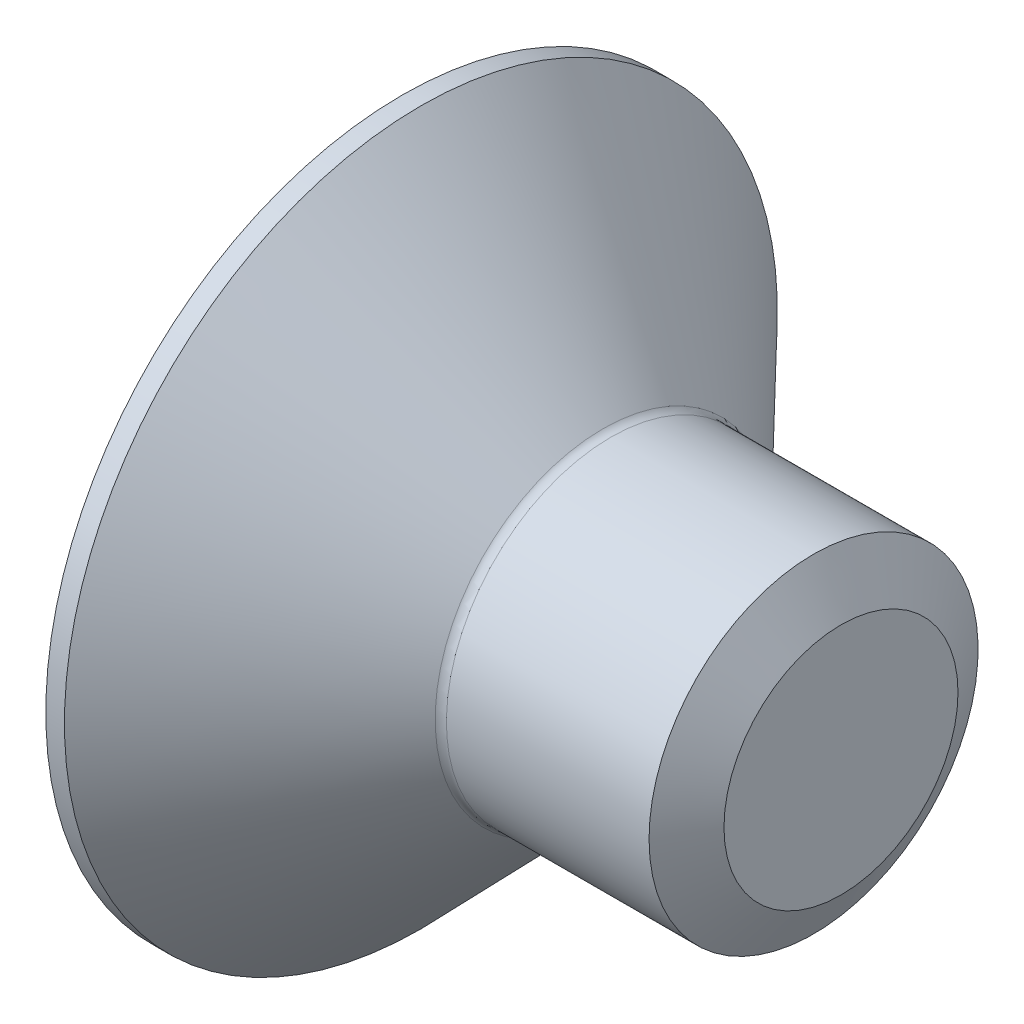
SolidWorks part; units mm, degrees
material "8.8级"
ref_plane "前视基准面" through (0, 0, 0) normal (0, 0, 1) x (1, 0, 0)
ref_plane "上视基准面" through (0, 0, 0) normal (0, 1, 0) x (1, 0, 0)
ref_plane "右视基准面" through (0, 0, 0) normal (1, 0, 0) x (0, 0, -1)
sketch "草图1" plane through (0, 0, 0) normal (0, 0, 1) x (1, 0, 0)
  line L0 (0, 1.5) -> (-2.0976, 1.5)
  line L1 (-2.1695, 1.5305) -> (-3.83, 3.25)
  line L2 (-3.83, 3.25) -> (-4, 3.25)
  line L3 (-4, 3.25) -> (-4, 0)
  line L4 (-4, 0) -> (0, 0)
  line L5 (0, 0) -> (0, 1.5)
  line L6 (0, 0) -> (-4, 0) construction
  arc A0 (-2.0976, 1.5) -> (-2.1695, 1.5305) centre (-2.0976, 1.6) cw
  point P9 (-2.14, 1.5)
  dimension "r" = 0.1
  dimension "k" = 1.86
  dimension "dk" = 6.5
  dimension "l" = 4
  dimension "d" = 3
  dimension "D5" = 46
revolve "旋转1" add sketch "草图1" angle 360 about L6
cosmetic thread "装饰螺纹线1" parameters "b"=6, "D2"=2.58
sketch "草图2" plane through (-4, 0, 0) normal (-1, 0, 0) x (0, 0, 1)
  line L1 (0, 1.1547) -> (-1, 0.5774)
  line L2 (-1, 0.5774) -> (-1, -0.5774)
  line L3 (-1, -0.5774) -> (0, -1.1547)
  line L4 (0, -1.1547) -> (1, -0.5774)
  line L5 (1, -0.5774) -> (1, 0.5774)
  line L6 (1, 0.5774) -> (0, 1.1547)
  circle A0 centre (0, 0) radius 1 construction
  dimension "s" = 2
extrude "切除-拉伸1" cut sketch "草图2" against normal blind 1.96
sketch "草图6" plane through (0, 0, 0) normal (0, 0, 1) x (1, 0, 0)
  line L0 (-2.9, 1.1547) -> (-2.2333, 0)
  line L1 (-2.2333, 0) -> (-1.74, 0)
  line L2 (-1.74, 0) -> (-1.74, 1.1547)
  line L3 (-1.74, 1.1547) -> (-2.9, 1.1547)
  line L4 (-4, 0) -> (-2.04, 0) construction
  line L5 (-4, 0) -> (-6.3, 0) construction
  dimension "t" = 1.1
  dimension "D1" = 60
  dimension "t1" = 1.96
  dimension "e-s" = 0.3
  dimension "e" = 2.3
revolve "旋转2" add sketch "草图6" angle 360 about L4
sketch "草图7" plane through (0, 0, 0) normal (0, 0, 1) x (1, 0, 0)
  line L0 (-4, 1.1547) -> (-4, 0)
  line L1 (-4, 0) -> (-3.67, 0)
  line L2 (-3.67, 0) -> (-4, 1.1547)
  line L3 (-4, 0) -> (-3.67, 0) construction
  dimension "e-s*1.1" = 0.33
revolve "切除-旋转2" cut sketch "草图7" angle 360 about L3
sketch "草图4" plane through (0, 0, 0) normal (0, 0, 1) x (1, 0, 0)
  line L0 (-0.25, 1.5) -> (0, 1.067)
  line L1 (0, -1.5) -> (0, 1.5) construction
  line L2 (0, 1.067) -> (0.25, 1.5)
  line L3 (0.25, 1.5) -> (-0.25, 1.5)
  line L4 (-0.25, 0) -> (0.25, 0) construction
  dimension "d" = 3
  dimension "p" = 0.5
revolve "切除-旋转1" cut sketch "草图4" angle 360 about L4
ref_axis "基准轴1" through (-21.1715, 0, 0) along (1, 0, 0)
pattern_linear "阵列(线性)2" [suppressed] count 12 spacing 0.5 along (-1, 0, 0) of bodies 104
equation "\"D2@装饰螺纹线1\" = \"d@草图1\" * 0.86"
equation "\"e-s@草图6\" = \"e@草图6\" - \"s@草图2\""
equation "\"t1@切除-拉伸1\" = \"k@草图1\" + 0.1"
equation "\"t1@草图6\" = \"t1@切除-拉伸1\""
equation "\"e-s*1.1@草图7\" = \"e-s@草图6\" * 1.1"
equation "\"d@草图4\" = \"d@草图1\""
equation "\"D3@阵列(线性)2\" = \"p@草图4\""
equation "\"D1@阵列(线性)2\" = \"b@装饰螺纹线1\" / \"p@草图4\""
